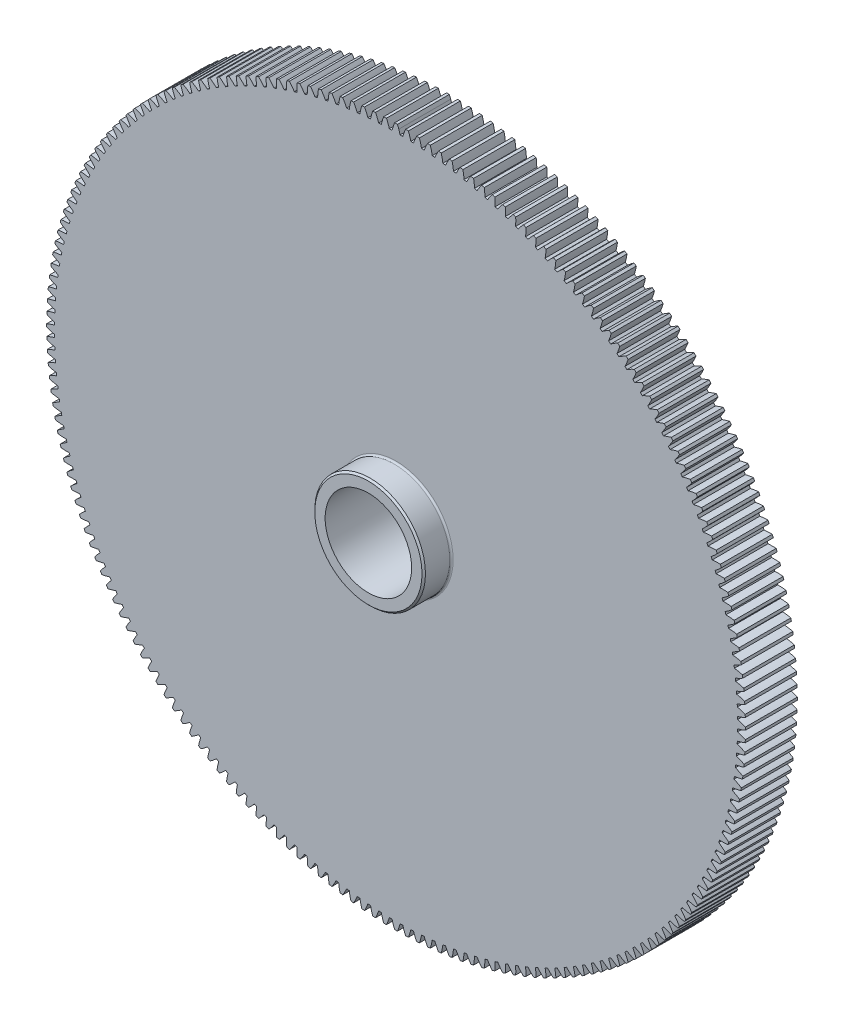
SolidWorks part; units mm, degrees
material "Сталь 45 ГОСТ 1050-88"
ref_plane "Front Plane" through (0, 0, 0) normal (0, 0, 1) x (1, 0, 0)
ref_plane "Top Plane" through (0, 0, 0) normal (0, 1, 0) x (1, 0, 0)
ref_plane "Right Plane" through (0, 0, 0) normal (1, 0, 0) x (0, 0, -1)
ref_plane "Ebene1" through (0, 0, 15) normal (0, 0, 1) x (1, 0, 0)
sketch "Skizze1" plane through (0, 0, 15) normal (0, 0, 1) x (1, 0, 0)
  arc A0 (-1.9388, 98.731) -> (-2.776, 100.9618) centre (-16.7744, 94.436) ccw
  arc A1 (-2.776, 100.9618) -> (-3.5689, 100.9369) centre (0, 0) ccw
  arc A2 (-3.5689, 100.9369) -> (-4.2644, 98.6579) centre (10.8116, 95.3029) ccw
  arc A3 (-4.2644, 98.6579) -> (-5.0391, 98.6213) centre (0, 0) ccw
  arc A4 (-5.0391, 98.6213) -> (-5.946, 100.8248) centre (-19.7324, 93.8625) ccw
  arc A5 (-5.946, 100.8248) -> (-6.7376, 100.775) centre (0, 0) ccw
  arc A6 (-6.7376, 100.775) -> (-7.3612, 98.4753) centre (7.8127, 95.5955) ccw
  arc A7 (-7.3612, 98.4753) -> (-8.1344, 98.4144) centre (0, 0) ccw
  arc A8 (-8.1344, 98.4144) -> (-9.11, 100.5883) centre (-22.671, 93.1964) ccw
  arc A9 (-9.11, 100.5883) -> (-9.8997, 100.5137) centre (0, 0) ccw
  arc A10 (-9.8997, 100.5137) -> (-10.4507, 98.1954) centre (4.8061, 95.7937) ccw
  arc A11 (-10.4507, 98.1954) -> (-11.2216, 98.1103) centre (0, 0) ccw
  arc A12 (-11.2216, 98.1103) -> (-12.2651, 100.2525) centre (-25.5872, 92.4383) ccw
  arc A13 (-12.2651, 100.2525) -> (-13.0521, 100.1531) centre (0, 0) ccw
  arc A14 (-13.0521, 100.1531) -> (-13.53, 97.8187) centre (1.7948, 95.8974) ccw
  arc A15 (-13.53, 97.8187) -> (-14.2978, 97.7094) centre (0, 0) ccw
  arc A16 (-14.2978, 97.7094) -> (-15.408, 99.8178) centre (-28.4781, 91.589) ccw
  arc A17 (-15.408, 99.8178) -> (-16.1915, 99.6937) centre (0, 0) ccw
  arc A18 (-16.1915, 99.6937) -> (-16.5959, 97.3455) centre (-1.2183, 95.9065) ccw
  arc A19 (-16.5959, 97.3455) -> (-17.3599, 97.2121) centre (0, 0) ccw
  arc A20 (-17.3599, 97.2121) -> (-18.5358, 99.2846) centre (-31.3409, 90.6492) ccw
  arc A21 (-18.5358, 99.2846) -> (-19.315, 99.1359) centre (0, 0) ccw
  arc A22 (-19.315, 99.1359) -> (-19.6454, 96.7761) centre (-4.2302, 95.8209) ccw
  arc A23 (-19.6454, 96.7761) -> (-20.4048, 96.6189) centre (0, 0) ccw
  arc A24 (-20.4048, 96.6189) -> (-21.6452, 98.6534) centre (-34.1728, 89.6201) ccw
  arc A25 (-21.6452, 98.6534) -> (-22.4194, 98.4803) centre (0, 0) ccw
  arc A26 (-22.4194, 98.4803) -> (-22.6755, 96.1113) centre (-7.2379, 95.6407) ccw
  arc A27 (-22.6755, 96.1113) -> (-23.4296, 95.9303) centre (0, 0) ccw
  arc A28 (-23.4296, 95.9303) -> (-24.7333, 97.9248) centre (-36.971, 88.5025) ccw
  arc A29 (-24.7333, 97.9248) -> (-25.5016, 97.7275) centre (0, 0) ccw
  arc A30 (-25.5016, 97.7275) -> (-25.6832, 95.3516) centre (-10.2385, 95.3662) ccw
  arc A31 (-25.6832, 95.3516) -> (-26.4313, 95.147) centre (0, 0) ccw
  arc A32 (-26.4313, 95.147) -> (-27.797, 97.0996) centre (-39.7327, 87.2975) ccw
  arc A33 (-27.797, 97.0996) -> (-28.5588, 96.8783) centre (0, 0) ccw
  arc A34 (-28.5588, 96.8783) -> (-28.6656, 94.4979) centre (-13.2289, 94.9975) ccw
  arc A35 (-28.6656, 94.4979) -> (-29.4069, 94.2698) centre (0, 0) ccw
  arc A36 (-29.4069, 94.2698) -> (-30.8333, 96.1785) centre (-42.4551, 86.0064) ccw
  arc A37 (-30.8333, 96.1785) -> (-31.5877, 95.9334) centre (0, 0) ccw
  arc A38 (-31.5877, 95.9334) -> (-31.6197, 93.5508) centre (-16.2064, 94.5351) ccw
  arc A39 (-31.6197, 93.5508) -> (-32.3535, 93.2996) centre (0, 0) ccw
  arc A40 (-32.3535, 93.2996) -> (-33.8391, 95.1626) centre (-45.1357, 84.6304) ccw
  arc A41 (-33.8391, 95.1626) -> (-34.5854, 94.8939) centre (0, 0) ccw
  arc A42 (-34.5854, 94.8939) -> (-34.5426, 92.5115) centre (-19.1678, 93.9794) ccw
  arc A43 (-34.5426, 92.5115) -> (-35.2681, 92.2373) centre (0, 0) ccw
  arc A44 (-35.2681, 92.2373) -> (-36.8115, 94.0527) centre (-47.7718, 83.1709) ccw
  arc A45 (-36.8115, 94.0527) -> (-37.5491, 93.7607) centre (0, 0) ccw
  arc A46 (-37.5491, 93.7607) -> (-37.4314, 91.3808) centre (-22.1103, 93.331) ccw
  arc A47 (-37.4314, 91.3808) -> (-38.148, 91.084) centre (0, 0) ccw
  arc A48 (-38.148, 91.084) -> (-39.7476, 92.85) centre (-50.3606, 81.6293) ccw
  arc A49 (-39.7476, 92.85) -> (-40.4756, 92.535) centre (0, 0) ccw
  arc A50 (-40.4756, 92.535) -> (-40.2833, 90.16) centre (-25.031, 92.5904) ccw
  arc A51 (-40.2833, 90.16) -> (-40.9902, 89.8408) centre (0, 0) ccw
  arc A52 (-40.9902, 89.8408) -> (-42.6445, 91.5557) centre (-52.8998, 80.0072) ccw
  arc A53 (-42.6445, 91.5557) -> (-43.3623, 91.218) centre (0, 0) ccw
  arc A54 (-43.3623, 91.218) -> (-43.0954, 88.8501) centre (-27.927, 91.7585) ccw
  arc A55 (-43.0954, 88.8501) -> (-43.7919, 88.5089) centre (0, 0) ccw
  arc A56 (-43.7919, 88.5089) -> (-45.4993, 90.171) centre (-55.3868, 78.3061) ccw
  arc A57 (-45.4993, 90.171) -> (-46.2061, 89.8109) centre (0, 0) ccw
  arc A58 (-46.2061, 89.8109) -> (-45.865, 87.4526) centre (-30.7954, 90.836) ccw
  arc A59 (-45.865, 87.4526) -> (-46.5504, 87.0897) centre (0, 0) ccw
  arc A60 (-46.5504, 87.0897) -> (-48.3092, 88.6974) centre (-57.8191, 76.5277) ccw
  arc A61 (-48.3092, 88.6974) -> (-49.0043, 88.3152) centre (0, 0) ccw
  arc A62 (-49.0043, 88.3152) -> (-48.5893, 85.9688) centre (-33.6334, 89.8239) ccw
  arc A63 (-48.5893, 85.9688) -> (-49.263, 85.5846) centre (0, 0) ccw
  arc A64 (-49.263, 85.5846) -> (-51.0714, 87.1362) centre (-60.1944, 74.6738) ccw
  arc A65 (-51.0714, 87.1362) -> (-51.7542, 86.7324) centre (0, 0) ccw
  arc A66 (-51.7542, 86.7324) -> (-51.2657, 84.4002) centre (-36.4383, 88.7231) ccw
  arc A67 (-51.2657, 84.4002) -> (-51.927, 83.9949) centre (0, 0) ccw
  arc A68 (-51.927, 83.9949) -> (-53.7832, 85.489) centre (-62.5103, 72.7462) ccw
  arc A69 (-53.7832, 85.489) -> (-54.453, 85.0639) centre (0, 0) ccw
  arc A70 (-54.453, 85.0639) -> (-53.8915, 82.7482) centre (-39.2071, 87.5348) ccw
  arc A71 (-53.8915, 82.7482) -> (-54.5397, 82.3224) centre (0, 0) ccw
  arc A72 (-54.5397, 82.3224) -> (-56.4419, 83.7574) centre (-64.7644, 70.7468) ccw
  arc A73 (-56.4419, 83.7574) -> (-57.098, 83.3116) centre (0, 0) ccw
  arc A74 (-57.098, 83.3116) -> (-56.4641, 81.0146) centre (-41.9373, 86.2601) ccw
  arc A75 (-56.4641, 81.0146) -> (-57.0986, 80.5687) centre (0, 0) ccw
  arc A76 (-57.0986, 80.5687) -> (-59.045, 81.9432) centre (-66.9547, 68.6776) ccw
  arc A77 (-59.045, 81.9432) -> (-59.6867, 81.477) centre (0, 0) ccw
  arc A78 (-59.6867, 81.477) -> (-58.9809, 79.2011) centre (-44.6261, 84.9002) ccw
  arc A79 (-58.9809, 79.2011) -> (-59.6011, 78.7354) centre (0, 0) ccw
  arc A80 (-59.6011, 78.7354) -> (-61.5897, 80.0481) centre (-69.0788, 66.5406) ccw
  arc A81 (-61.5897, 80.0481) -> (-62.2165, 79.5619) centre (0, 0) ccw
  arc A82 (-62.2165, 79.5619) -> (-61.4396, 77.3094) centre (-47.2709, 83.4566) ccw
  arc A83 (-61.4396, 77.3094) -> (-62.0449, 76.8244) centre (0, 0) ccw
  arc A84 (-62.0449, 76.8244) -> (-64.0737, 78.0741) centre (-71.1349, 64.3379) ccw
  arc A85 (-64.0737, 78.0741) -> (-64.6849, 77.5684) centre (0, 0) ccw
  arc A86 (-64.6849, 77.5684) -> (-63.8376, 75.3414) centre (-49.869, 81.9306) ccw
  arc A87 (-63.8376, 75.3414) -> (-64.4274, 74.8377) centre (0, 0) ccw
  arc A88 (-64.4274, 74.8377) -> (-66.4945, 76.0229) centre (-73.1207, 62.0718) ccw
  arc A89 (-66.4945, 76.0229) -> (-67.0895, 75.4983) centre (0, 0) ccw
  arc A90 (-67.0895, 75.4983) -> (-66.1727, 73.299) centre (-52.4179, 80.3237) ccw
  arc A91 (-66.1727, 73.299) -> (-66.7463, 72.777) centre (0, 0) ccw
  arc A92 (-66.7463, 72.777) -> (-68.8496, 73.8968) centre (-75.0343, 59.7444) ccw
  arc A93 (-68.8496, 73.8968) -> (-69.4279, 73.3538) centre (0, 0) ccw
  arc A94 (-69.4279, 73.3538) -> (-68.4424, 71.1843) centre (-54.915, 78.6376) ccw
  arc A95 (-68.4424, 71.1843) -> (-68.9993, 70.6446) centre (0, 0) ccw
  arc A96 (-68.9993, 70.6446) -> (-71.1368, 71.6977) centre (-76.8739, 57.358) ccw
  arc A97 (-71.1368, 71.6977) -> (-71.6977, 71.1368) centre (0, 0) ccw
  arc A98 (-71.6977, 71.1368) -> (-70.6446, 68.9993) centre (-57.358, 76.8739) ccw
  arc A99 (-70.6446, 68.9993) -> (-71.1843, 68.4424) centre (0, 0) ccw
  arc A100 (-71.1843, 68.4424) -> (-73.3538, 69.4279) centre (-78.6376, 54.915) ccw
  arc A101 (-73.3538, 69.4279) -> (-73.8968, 68.8496) centre (0, 0) ccw
  arc A102 (-73.8968, 68.8496) -> (-72.777, 66.7463) centre (-59.7444, 75.0343) ccw
  arc A103 (-72.777, 66.7463) -> (-73.299, 66.1727) centre (0, 0) ccw
  arc A104 (-73.299, 66.1727) -> (-75.4983, 67.0895) centre (-80.3237, 52.4179) ccw
  arc A105 (-75.4983, 67.0895) -> (-76.0229, 66.4945) centre (0, 0) ccw
  arc A106 (-76.0229, 66.4945) -> (-74.8377, 64.4274) centre (-62.0718, 73.1207) ccw
  arc A107 (-74.8377, 64.4274) -> (-75.3414, 63.8376) centre (0, 0) ccw
  arc A108 (-75.3414, 63.8376) -> (-77.5684, 64.6849) centre (-81.9306, 49.869) ccw
  arc A109 (-77.5684, 64.6849) -> (-78.0741, 64.0737) centre (0, 0) ccw
  arc A110 (-78.0741, 64.0737) -> (-76.8244, 62.0449) centre (-64.3379, 71.1349) ccw
  arc A111 (-76.8244, 62.0449) -> (-77.3094, 61.4396) centre (0, 0) ccw
  arc A112 (-77.3094, 61.4396) -> (-79.5619, 62.2165) centre (-83.4566, 47.2709) ccw
  arc A113 (-79.5619, 62.2165) -> (-80.0481, 61.5897) centre (0, 0) ccw
  arc A114 (-80.0481, 61.5897) -> (-78.7354, 59.6011) centre (-66.5406, 69.0788) ccw
  arc A115 (-78.7354, 59.6011) -> (-79.2011, 58.9809) centre (0, 0) ccw
  arc A116 (-79.2011, 58.9809) -> (-81.477, 59.6867) centre (-84.9002, 44.6261) ccw
  arc A117 (-81.477, 59.6867) -> (-81.9432, 59.045) centre (0, 0) ccw
  arc A118 (-81.9432, 59.045) -> (-80.5687, 57.0986) centre (-68.6776, 66.9547) ccw
  arc A119 (-80.5687, 57.0986) -> (-81.0146, 56.4641) centre (0, 0) ccw
  arc A120 (-81.0146, 56.4641) -> (-83.3116, 57.098) centre (-86.2601, 41.9373) ccw
  arc A121 (-83.3116, 57.098) -> (-83.7574, 56.4419) centre (0, 0) ccw
  arc A122 (-83.7574, 56.4419) -> (-82.3224, 54.5397) centre (-70.7468, 64.7644) ccw
  arc A123 (-82.3224, 54.5397) -> (-82.7482, 53.8915) centre (0, 0) ccw
  arc A124 (-82.7482, 53.8915) -> (-85.0639, 54.453) centre (-87.5348, 39.2071) ccw
  arc A125 (-85.0639, 54.453) -> (-85.489, 53.7832) centre (0, 0) ccw
  arc A126 (-85.489, 53.7832) -> (-83.9949, 51.927) centre (-72.7462, 62.5103) ccw
  arc A127 (-83.9949, 51.927) -> (-84.4002, 51.2657) centre (0, 0) ccw
  arc A128 (-84.4002, 51.2657) -> (-86.7324, 51.7542) centre (-88.7231, 36.4383) ccw
  arc A129 (-86.7324, 51.7542) -> (-87.1362, 51.0714) centre (0, 0) ccw
  arc A130 (-87.1362, 51.0714) -> (-85.5846, 49.263) centre (-74.6738, 60.1944) ccw
  arc A131 (-85.5846, 49.263) -> (-85.9688, 48.5893) centre (0, 0) ccw
  arc A132 (-85.9688, 48.5893) -> (-88.3152, 49.0043) centre (-89.8239, 33.6334) ccw
  arc A133 (-88.3152, 49.0043) -> (-88.6974, 48.3092) centre (0, 0) ccw
  arc A134 (-88.6974, 48.3092) -> (-87.0897, 46.5504) centre (-76.5277, 57.8191) ccw
  arc A135 (-87.0897, 46.5504) -> (-87.4526, 45.865) centre (0, 0) ccw
  arc A136 (-87.4526, 45.865) -> (-89.8109, 46.2061) centre (-90.836, 30.7954) ccw
  arc A137 (-89.8109, 46.2061) -> (-90.171, 45.4993) centre (0, 0) ccw
  arc A138 (-90.171, 45.4993) -> (-88.5089, 43.7919) centre (-78.3061, 55.3868) ccw
  arc A139 (-88.5089, 43.7919) -> (-88.8501, 43.0954) centre (0, 0) ccw
  arc A140 (-88.8501, 43.0954) -> (-91.218, 43.3623) centre (-91.7585, 27.927) ccw
  arc A141 (-91.218, 43.3623) -> (-91.5557, 42.6445) centre (0, 0) ccw
  arc A142 (-91.5557, 42.6445) -> (-89.8408, 40.9902) centre (-80.0072, 52.8998) ccw
  arc A143 (-89.8408, 40.9902) -> (-90.16, 40.2833) centre (0, 0) ccw
  arc A144 (-90.16, 40.2833) -> (-92.535, 40.4756) centre (-92.5904, 25.031) ccw
  arc A145 (-92.535, 40.4756) -> (-92.85, 39.7476) centre (0, 0) ccw
  arc A146 (-92.85, 39.7476) -> (-91.084, 38.148) centre (-81.6293, 50.3606) ccw
  arc A147 (-91.084, 38.148) -> (-91.3808, 37.4314) centre (0, 0) ccw
  arc A148 (-91.3808, 37.4314) -> (-93.7607, 37.5491) centre (-93.331, 22.1103) ccw
  arc A149 (-93.7607, 37.5491) -> (-94.0527, 36.8115) centre (0, 0) ccw
  arc A150 (-94.0527, 36.8115) -> (-92.2373, 35.2681) centre (-83.1709, 47.7718) ccw
  arc A151 (-92.2373, 35.2681) -> (-92.5115, 34.5426) centre (0, 0) ccw
  arc A152 (-92.5115, 34.5426) -> (-94.8939, 34.5854) centre (-93.9794, 19.1678) ccw
  arc A153 (-94.8939, 34.5854) -> (-95.1626, 33.8391) centre (0, 0) ccw
  arc A154 (-95.1626, 33.8391) -> (-93.2996, 32.3535) centre (-84.6304, 45.1357) ccw
  arc A155 (-93.2996, 32.3535) -> (-93.5508, 31.6197) centre (0, 0) ccw
  arc A156 (-93.5508, 31.6197) -> (-95.9334, 31.5877) centre (-94.5351, 16.2064) ccw
  arc A157 (-95.9334, 31.5877) -> (-96.1785, 30.8333) centre (0, 0) ccw
  arc A158 (-96.1785, 30.8333) -> (-94.2698, 29.4069) centre (-86.0064, 42.4551) ccw
  arc A159 (-94.2698, 29.4069) -> (-94.4979, 28.6656) centre (0, 0) ccw
  arc A160 (-94.4979, 28.6656) -> (-96.8783, 28.5588) centre (-94.9975, 13.2289) ccw
  arc A161 (-96.8783, 28.5588) -> (-97.0996, 27.797) centre (0, 0) ccw
  arc A162 (-97.0996, 27.797) -> (-95.147, 26.4313) centre (-87.2975, 39.7327) ccw
  arc A163 (-95.147, 26.4313) -> (-95.3516, 25.6832) centre (0, 0) ccw
  arc A164 (-95.3516, 25.6832) -> (-97.7275, 25.5016) centre (-95.3662, 10.2385) ccw
  arc A165 (-97.7275, 25.5016) -> (-97.9248, 24.7333) centre (0, 0) ccw
  arc A166 (-97.9248, 24.7333) -> (-95.9303, 23.4296) centre (-88.5025, 36.971) ccw
  arc A167 (-95.9303, 23.4296) -> (-96.1113, 22.6755) centre (0, 0) ccw
  arc A168 (-96.1113, 22.6755) -> (-98.4803, 22.4194) centre (-95.6407, 7.2379) ccw
  arc A169 (-98.4803, 22.4194) -> (-98.6534, 21.6452) centre (0, 0) ccw
  arc A170 (-98.6534, 21.6452) -> (-96.6189, 20.4048) centre (-89.6201, 34.1728) ccw
  arc A171 (-96.6189, 20.4048) -> (-96.7761, 19.6454) centre (0, 0) ccw
  arc A172 (-96.7761, 19.6454) -> (-99.1359, 19.315) centre (-95.8209, 4.2302) ccw
  arc A173 (-99.1359, 19.315) -> (-99.2846, 18.5358) centre (0, 0) ccw
  arc A174 (-99.2846, 18.5358) -> (-97.2121, 17.3599) centre (-90.6492, 31.3409) ccw
  arc A175 (-97.2121, 17.3599) -> (-97.3455, 16.5959) centre (0, 0) ccw
  arc A176 (-97.3455, 16.5959) -> (-99.6937, 16.1915) centre (-95.9065, 1.2183) ccw
  arc A177 (-99.6937, 16.1915) -> (-99.8178, 15.408) centre (0, 0) ccw
  arc A178 (-99.8178, 15.408) -> (-97.7094, 14.2978) centre (-91.589, 28.4781) ccw
  arc A179 (-97.7094, 14.2978) -> (-97.8187, 13.53) centre (0, 0) ccw
  arc A180 (-97.8187, 13.53) -> (-100.1531, 13.0521) centre (-95.8974, -1.7948) ccw
  arc A181 (-100.1531, 13.0521) -> (-100.2525, 12.2651) centre (0, 0) ccw
  arc A182 (-100.2525, 12.2651) -> (-98.1103, 11.2216) centre (-92.4383, 25.5872) ccw
  arc A183 (-98.1103, 11.2216) -> (-98.1954, 10.4507) centre (0, 0) ccw
  arc A184 (-98.1954, 10.4507) -> (-100.5137, 9.8997) centre (-95.7937, -4.8061) ccw
  arc A185 (-100.5137, 9.8997) -> (-100.5883, 9.11) centre (0, 0) ccw
  arc A186 (-100.5883, 9.11) -> (-98.4144, 8.1344) centre (-93.1964, 22.671) ccw
  arc A187 (-98.4144, 8.1344) -> (-98.4753, 7.3612) centre (0, 0) ccw
  arc A188 (-98.4753, 7.3612) -> (-100.775, 6.7376) centre (-95.5955, -7.8127) ccw
  arc A189 (-100.775, 6.7376) -> (-100.8248, 5.946) centre (0, 0) ccw
  arc A190 (-100.8248, 5.946) -> (-98.6213, 5.0391) centre (-93.8625, 19.7324) ccw
  arc A191 (-98.6213, 5.0391) -> (-98.6579, 4.2644) centre (0, 0) ccw
  arc A192 (-98.6579, 4.2644) -> (-100.9369, 3.5689) centre (-95.3029, -10.8116) ccw
  arc A193 (-100.9369, 3.5689) -> (-100.9618, 2.776) centre (0, 0) ccw
  arc A194 (-100.9618, 2.776) -> (-98.731, 1.9388) centre (-94.436, 16.7744) ccw
  arc A195 (-98.731, 1.9388) -> (-98.7431, 1.1633) centre (0, 0) ccw
  arc A196 (-98.7431, 1.1633) -> (-100.9992, 0.3966) centre (-94.9163, -13.7998) ccw
  arc A197 (-100.9992, 0.3966) -> (-100.9992, -0.3966) centre (0, 0) ccw
  arc A198 (-100.9992, -0.3966) -> (-98.7431, -1.1633) centre (-94.9163, 13.7998) ccw
  arc A199 (-98.7431, -1.1633) -> (-98.731, -1.9388) centre (0, 0) ccw
  arc A200 (-98.731, -1.9388) -> (-100.9618, -2.776) centre (-94.436, -16.7744) ccw
  arc A201 (-100.9618, -2.776) -> (-100.9369, -3.5689) centre (0, 0) ccw
  arc A202 (-100.9369, -3.5689) -> (-98.6579, -4.2644) centre (-95.3029, 10.8116) ccw
  arc A203 (-98.6579, -4.2644) -> (-98.6213, -5.0391) centre (0, 0) ccw
  arc A204 (-98.6213, -5.0391) -> (-100.8248, -5.946) centre (-93.8625, -19.7324) ccw
  arc A205 (-100.8248, -5.946) -> (-100.775, -6.7376) centre (0, 0) ccw
  arc A206 (-100.775, -6.7376) -> (-98.4753, -7.3612) centre (-95.5955, 7.8127) ccw
  arc A207 (-98.4753, -7.3612) -> (-98.4144, -8.1344) centre (0, 0) ccw
  arc A208 (-98.4144, -8.1344) -> (-100.5883, -9.11) centre (-93.1964, -22.671) ccw
  arc A209 (-100.5883, -9.11) -> (-100.5137, -9.8997) centre (0, 0) ccw
  arc A210 (-100.5137, -9.8997) -> (-98.1954, -10.4507) centre (-95.7937, 4.8061) ccw
  arc A211 (-98.1954, -10.4507) -> (-98.1103, -11.2216) centre (0, 0) ccw
  arc A212 (-98.1103, -11.2216) -> (-100.2525, -12.2651) centre (-92.4383, -25.5872) ccw
  arc A213 (-100.2525, -12.2651) -> (-100.1531, -13.0521) centre (0, 0) ccw
  arc A214 (-100.1531, -13.0521) -> (-97.8187, -13.53) centre (-95.8974, 1.7948) ccw
  arc A215 (-97.8187, -13.53) -> (-97.7094, -14.2978) centre (0, 0) ccw
  arc A216 (-97.7094, -14.2978) -> (-99.8178, -15.408) centre (-91.589, -28.4781) ccw
  arc A217 (-99.8178, -15.408) -> (-99.6937, -16.1915) centre (0, 0) ccw
  arc A218 (-99.6937, -16.1915) -> (-97.3455, -16.5959) centre (-95.9065, -1.2183) ccw
  arc A219 (-97.3455, -16.5959) -> (-97.2121, -17.3599) centre (0, 0) ccw
  arc A220 (-97.2121, -17.3599) -> (-99.2846, -18.5358) centre (-90.6492, -31.3409) ccw
  arc A221 (-99.2846, -18.5358) -> (-99.1359, -19.315) centre (0, 0) ccw
  arc A222 (-99.1359, -19.315) -> (-96.7761, -19.6454) centre (-95.8209, -4.2302) ccw
  arc A223 (-96.7761, -19.6454) -> (-96.6189, -20.4048) centre (0, 0) ccw
  arc A224 (-96.6189, -20.4048) -> (-98.6534, -21.6452) centre (-89.6201, -34.1728) ccw
  arc A225 (-98.6534, -21.6452) -> (-98.4803, -22.4194) centre (0, 0) ccw
  arc A226 (-98.4803, -22.4194) -> (-96.1113, -22.6755) centre (-95.6407, -7.2379) ccw
  arc A227 (-96.1113, -22.6755) -> (-95.9303, -23.4296) centre (0, 0) ccw
  arc A228 (-95.9303, -23.4296) -> (-97.9248, -24.7333) centre (-88.5025, -36.971) ccw
  arc A229 (-97.9248, -24.7333) -> (-97.7275, -25.5016) centre (0, 0) ccw
  arc A230 (-97.7275, -25.5016) -> (-95.3516, -25.6832) centre (-95.3662, -10.2385) ccw
  arc A231 (-95.3516, -25.6832) -> (-95.147, -26.4313) centre (0, 0) ccw
  arc A232 (-95.147, -26.4313) -> (-97.0996, -27.797) centre (-87.2975, -39.7327) ccw
  arc A233 (-97.0996, -27.797) -> (-96.8783, -28.5588) centre (0, 0) ccw
  arc A234 (-96.8783, -28.5588) -> (-94.4979, -28.6656) centre (-94.9975, -13.2289) ccw
  arc A235 (-94.4979, -28.6656) -> (-94.2698, -29.4069) centre (0, 0) ccw
  arc A236 (-94.2698, -29.4069) -> (-96.1785, -30.8333) centre (-86.0064, -42.4551) ccw
  arc A237 (-96.1785, -30.8333) -> (-95.9334, -31.5877) centre (0, 0) ccw
  arc A238 (-95.9334, -31.5877) -> (-93.5508, -31.6197) centre (-94.5351, -16.2064) ccw
  arc A239 (-93.5508, -31.6197) -> (-93.2996, -32.3535) centre (0, 0) ccw
  arc A240 (-93.2996, -32.3535) -> (-95.1626, -33.8391) centre (-84.6304, -45.1357) ccw
  arc A241 (-95.1626, -33.8391) -> (-94.8939, -34.5854) centre (0, 0) ccw
  arc A242 (-94.8939, -34.5854) -> (-92.5115, -34.5426) centre (-93.9794, -19.1678) ccw
  arc A243 (-92.5115, -34.5426) -> (-92.2373, -35.2681) centre (0, 0) ccw
  arc A244 (-92.2373, -35.2681) -> (-94.0527, -36.8115) centre (-83.1709, -47.7718) ccw
  arc A245 (-94.0527, -36.8115) -> (-93.7607, -37.5491) centre (0, 0) ccw
  arc A246 (-93.7607, -37.5491) -> (-91.3808, -37.4314) centre (-93.331, -22.1103) ccw
  arc A247 (-91.3808, -37.4314) -> (-91.084, -38.148) centre (0, 0) ccw
  arc A248 (-91.084, -38.148) -> (-92.85, -39.7476) centre (-81.6293, -50.3606) ccw
  arc A249 (-92.85, -39.7476) -> (-92.535, -40.4756) centre (0, 0) ccw
  arc A250 (-92.535, -40.4756) -> (-90.16, -40.2833) centre (-92.5904, -25.031) ccw
  arc A251 (-90.16, -40.2833) -> (-89.8408, -40.9902) centre (0, 0) ccw
  arc A252 (-89.8408, -40.9902) -> (-91.5557, -42.6445) centre (-80.0072, -52.8998) ccw
  arc A253 (-91.5557, -42.6445) -> (-91.218, -43.3623) centre (0, 0) ccw
  arc A254 (-91.218, -43.3623) -> (-88.8501, -43.0954) centre (-91.7585, -27.927) ccw
  arc A255 (-88.8501, -43.0954) -> (-88.5089, -43.7919) centre (0, 0) ccw
  arc A256 (-88.5089, -43.7919) -> (-90.171, -45.4993) centre (-78.3061, -55.3868) ccw
  arc A257 (-90.171, -45.4993) -> (-89.8109, -46.2061) centre (0, 0) ccw
  arc A258 (-89.8109, -46.2061) -> (-87.4526, -45.865) centre (-90.836, -30.7954) ccw
  arc A259 (-87.4526, -45.865) -> (-87.0897, -46.5504) centre (0, 0) ccw
  arc A260 (-87.0897, -46.5504) -> (-88.6974, -48.3092) centre (-76.5277, -57.8191) ccw
  arc A261 (-88.6974, -48.3092) -> (-88.3152, -49.0043) centre (0, 0) ccw
  arc A262 (-88.3152, -49.0043) -> (-85.9688, -48.5893) centre (-89.8239, -33.6334) ccw
  arc A263 (-85.9688, -48.5893) -> (-85.5846, -49.263) centre (0, 0) ccw
  arc A264 (-85.5846, -49.263) -> (-87.1362, -51.0714) centre (-74.6738, -60.1944) ccw
  arc A265 (-87.1362, -51.0714) -> (-86.7324, -51.7542) centre (0, 0) ccw
  arc A266 (-86.7324, -51.7542) -> (-84.4002, -51.2657) centre (-88.7231, -36.4383) ccw
  arc A267 (-84.4002, -51.2657) -> (-83.9949, -51.927) centre (0, 0) ccw
  arc A268 (-83.9949, -51.927) -> (-85.489, -53.7832) centre (-72.7462, -62.5103) ccw
  arc A269 (-85.489, -53.7832) -> (-85.0639, -54.453) centre (0, 0) ccw
  arc A270 (-85.0639, -54.453) -> (-82.7482, -53.8915) centre (-87.5348, -39.2071) ccw
  arc A271 (-82.7482, -53.8915) -> (-82.3224, -54.5397) centre (0, 0) ccw
  arc A272 (-82.3224, -54.5397) -> (-83.7574, -56.4419) centre (-70.7468, -64.7644) ccw
  arc A273 (-83.7574, -56.4419) -> (-83.3116, -57.098) centre (0, 0) ccw
  arc A274 (-83.3116, -57.098) -> (-81.0146, -56.4641) centre (-86.2601, -41.9373) ccw
  arc A275 (-81.0146, -56.4641) -> (-80.5687, -57.0986) centre (0, 0) ccw
  arc A276 (-80.5687, -57.0986) -> (-81.9432, -59.045) centre (-68.6776, -66.9547) ccw
  arc A277 (-81.9432, -59.045) -> (-81.477, -59.6867) centre (0, 0) ccw
  arc A278 (-81.477, -59.6867) -> (-79.2011, -58.9809) centre (-84.9002, -44.6261) ccw
  arc A279 (-79.2011, -58.9809) -> (-78.7354, -59.6011) centre (0, 0) ccw
  arc A280 (-78.7354, -59.6011) -> (-80.0481, -61.5897) centre (-66.5406, -69.0788) ccw
  arc A281 (-80.0481, -61.5897) -> (-79.5619, -62.2165) centre (0, 0) ccw
  arc A282 (-79.5619, -62.2165) -> (-77.3094, -61.4396) centre (-83.4566, -47.2709) ccw
  arc A283 (-77.3094, -61.4396) -> (-76.8244, -62.0449) centre (0, 0) ccw
  arc A284 (-76.8244, -62.0449) -> (-78.0741, -64.0737) centre (-64.3379, -71.1349) ccw
  arc A285 (-78.0741, -64.0737) -> (-77.5684, -64.6849) centre (0, 0) ccw
  arc A286 (-77.5684, -64.6849) -> (-75.3414, -63.8376) centre (-81.9306, -49.869) ccw
  arc A287 (-75.3414, -63.8376) -> (-74.8377, -64.4274) centre (0, 0) ccw
  arc A288 (-74.8377, -64.4274) -> (-76.0229, -66.4945) centre (-62.0718, -73.1207) ccw
  arc A289 (-76.0229, -66.4945) -> (-75.4983, -67.0895) centre (0, 0) ccw
  arc A290 (-75.4983, -67.0895) -> (-73.299, -66.1727) centre (-80.3237, -52.4179) ccw
  arc A291 (-73.299, -66.1727) -> (-72.777, -66.7463) centre (0, 0) ccw
  arc A292 (-72.777, -66.7463) -> (-73.8968, -68.8496) centre (-59.7444, -75.0343) ccw
  arc A293 (-73.8968, -68.8496) -> (-73.3538, -69.4279) centre (0, 0) ccw
  arc A294 (-73.3538, -69.4279) -> (-71.1843, -68.4424) centre (-78.6376, -54.915) ccw
  arc A295 (-71.1843, -68.4424) -> (-70.6446, -68.9993) centre (0, 0) ccw
  arc A296 (-70.6446, -68.9993) -> (-71.6977, -71.1368) centre (-57.358, -76.8739) ccw
  arc A297 (-71.6977, -71.1368) -> (-71.1368, -71.6977) centre (0, 0) ccw
  arc A298 (-71.1368, -71.6977) -> (-68.9993, -70.6446) centre (-76.8739, -57.358) ccw
  arc A299 (-68.9993, -70.6446) -> (-68.4424, -71.1843) centre (0, 0) ccw
  arc A300 (-68.4424, -71.1843) -> (-69.4279, -73.3538) centre (-54.915, -78.6376) ccw
  arc A301 (-69.4279, -73.3538) -> (-68.8496, -73.8968) centre (0, 0) ccw
  arc A302 (-68.8496, -73.8968) -> (-66.7463, -72.777) centre (-75.0343, -59.7444) ccw
  arc A303 (-66.7463, -72.777) -> (-66.1727, -73.299) centre (0, 0) ccw
  arc A304 (-66.1727, -73.299) -> (-67.0895, -75.4983) centre (-52.4179, -80.3237) ccw
  arc A305 (-67.0895, -75.4983) -> (-66.4945, -76.0229) centre (0, 0) ccw
  arc A306 (-66.4945, -76.0229) -> (-64.4274, -74.8377) centre (-73.1207, -62.0718) ccw
  arc A307 (-64.4274, -74.8377) -> (-63.8376, -75.3414) centre (0, 0) ccw
  arc A308 (-63.8376, -75.3414) -> (-64.6849, -77.5684) centre (-49.869, -81.9306) ccw
  arc A309 (-64.6849, -77.5684) -> (-64.0737, -78.0741) centre (0, 0) ccw
  arc A310 (-64.0737, -78.0741) -> (-62.0449, -76.8244) centre (-71.1349, -64.3379) ccw
  arc A311 (-62.0449, -76.8244) -> (-61.4396, -77.3094) centre (0, 0) ccw
  arc A312 (-61.4396, -77.3094) -> (-62.2165, -79.5619) centre (-47.2709, -83.4566) ccw
  arc A313 (-62.2165, -79.5619) -> (-61.5897, -80.0481) centre (0, 0) ccw
  arc A314 (-61.5897, -80.0481) -> (-59.6011, -78.7354) centre (-69.0788, -66.5406) ccw
  arc A315 (-59.6011, -78.7354) -> (-58.9809, -79.2011) centre (0, 0) ccw
  arc A316 (-58.9809, -79.2011) -> (-59.6867, -81.477) centre (-44.6261, -84.9002) ccw
  arc A317 (-59.6867, -81.477) -> (-59.045, -81.9432) centre (0, 0) ccw
  arc A318 (-59.045, -81.9432) -> (-57.0986, -80.5687) centre (-66.9547, -68.6776) ccw
  arc A319 (-57.0986, -80.5687) -> (-56.4641, -81.0146) centre (0, 0) ccw
  arc A320 (-56.4641, -81.0146) -> (-57.098, -83.3116) centre (-41.9373, -86.2601) ccw
  arc A321 (-57.098, -83.3116) -> (-56.4419, -83.7574) centre (0, 0) ccw
  arc A322 (-56.4419, -83.7574) -> (-54.5397, -82.3224) centre (-64.7644, -70.7468) ccw
  arc A323 (-54.5397, -82.3224) -> (-53.8915, -82.7482) centre (0, 0) ccw
  arc A324 (-53.8915, -82.7482) -> (-54.453, -85.0639) centre (-39.2071, -87.5348) ccw
  arc A325 (-54.453, -85.0639) -> (-53.7832, -85.489) centre (0, 0) ccw
  arc A326 (-53.7832, -85.489) -> (-51.927, -83.9949) centre (-62.5103, -72.7462) ccw
  arc A327 (-51.927, -83.9949) -> (-51.2657, -84.4002) centre (0, 0) ccw
  arc A328 (-51.2657, -84.4002) -> (-51.7542, -86.7324) centre (-36.4383, -88.7231) ccw
  arc A329 (-51.7542, -86.7324) -> (-51.0714, -87.1362) centre (0, 0) ccw
  arc A330 (-51.0714, -87.1362) -> (-49.263, -85.5846) centre (-60.1944, -74.6738) ccw
  arc A331 (-49.263, -85.5846) -> (-48.5893, -85.9688) centre (0, 0) ccw
  arc A332 (-48.5893, -85.9688) -> (-49.0043, -88.3152) centre (-33.6334, -89.8239) ccw
  arc A333 (-49.0043, -88.3152) -> (-48.3092, -88.6974) centre (0, 0) ccw
  arc A334 (-48.3092, -88.6974) -> (-46.5504, -87.0897) centre (-57.8191, -76.5277) ccw
  arc A335 (-46.5504, -87.0897) -> (-45.865, -87.4526) centre (0, 0) ccw
  arc A336 (-45.865, -87.4526) -> (-46.2061, -89.8109) centre (-30.7954, -90.836) ccw
  arc A337 (-46.2061, -89.8109) -> (-45.4993, -90.171) centre (0, 0) ccw
  arc A338 (-45.4993, -90.171) -> (-43.7919, -88.5089) centre (-55.3868, -78.3061) ccw
  arc A339 (-43.7919, -88.5089) -> (-43.0954, -88.8501) centre (0, 0) ccw
  arc A340 (-43.0954, -88.8501) -> (-43.3623, -91.218) centre (-27.927, -91.7585) ccw
  arc A341 (-43.3623, -91.218) -> (-42.6445, -91.5557) centre (0, 0) ccw
  arc A342 (-42.6445, -91.5557) -> (-40.9902, -89.8408) centre (-52.8998, -80.0072) ccw
  arc A343 (-40.9902, -89.8408) -> (-40.2833, -90.16) centre (0, 0) ccw
  arc A344 (-40.2833, -90.16) -> (-40.4756, -92.535) centre (-25.031, -92.5904) ccw
  arc A345 (-40.4756, -92.535) -> (-39.7476, -92.85) centre (0, 0) ccw
  arc A346 (-39.7476, -92.85) -> (-38.148, -91.084) centre (-50.3606, -81.6293) ccw
  arc A347 (-38.148, -91.084) -> (-37.4314, -91.3808) centre (0, 0) ccw
  arc A348 (-37.4314, -91.3808) -> (-37.5491, -93.7607) centre (-22.1103, -93.331) ccw
  arc A349 (-37.5491, -93.7607) -> (-36.8115, -94.0527) centre (0, 0) ccw
  arc A350 (-36.8115, -94.0527) -> (-35.2681, -92.2373) centre (-47.7718, -83.1709) ccw
  arc A351 (-35.2681, -92.2373) -> (-34.5426, -92.5115) centre (0, 0) ccw
  arc A352 (-34.5426, -92.5115) -> (-34.5854, -94.8939) centre (-19.1678, -93.9794) ccw
  arc A353 (-34.5854, -94.8939) -> (-33.8391, -95.1626) centre (0, 0) ccw
  arc A354 (-33.8391, -95.1626) -> (-32.3535, -93.2996) centre (-45.1357, -84.6304) ccw
  arc A355 (-32.3535, -93.2996) -> (-31.6197, -93.5508) centre (0, 0) ccw
  arc A356 (-31.6197, -93.5508) -> (-31.5877, -95.9334) centre (-16.2064, -94.5351) ccw
  arc A357 (-31.5877, -95.9334) -> (-30.8333, -96.1785) centre (0, 0) ccw
  arc A358 (-30.8333, -96.1785) -> (-29.4069, -94.2698) centre (-42.4551, -86.0064) ccw
  arc A359 (-29.4069, -94.2698) -> (-28.6656, -94.4979) centre (0, 0) ccw
  arc A360 (-28.6656, -94.4979) -> (-28.5588, -96.8783) centre (-13.2289, -94.9975) ccw
  arc A361 (-28.5588, -96.8783) -> (-27.797, -97.0996) centre (0, 0) ccw
  arc A362 (-27.797, -97.0996) -> (-26.4313, -95.147) centre (-39.7327, -87.2975) ccw
  arc A363 (-26.4313, -95.147) -> (-25.6832, -95.3516) centre (0, 0) ccw
  arc A364 (-25.6832, -95.3516) -> (-25.5016, -97.7275) centre (-10.2385, -95.3662) ccw
  arc A365 (-25.5016, -97.7275) -> (-24.7333, -97.9248) centre (0, 0) ccw
  arc A366 (-24.7333, -97.9248) -> (-23.4296, -95.9303) centre (-36.971, -88.5025) ccw
  arc A367 (-23.4296, -95.9303) -> (-22.6755, -96.1113) centre (0, 0) ccw
  arc A368 (-22.6755, -96.1113) -> (-22.4194, -98.4803) centre (-7.2379, -95.6407) ccw
  arc A369 (-22.4194, -98.4803) -> (-21.6452, -98.6534) centre (0, 0) ccw
  arc A370 (-21.6452, -98.6534) -> (-20.4048, -96.6189) centre (-34.1728, -89.6201) ccw
  arc A371 (-20.4048, -96.6189) -> (-19.6454, -96.7761) centre (0, 0) ccw
  arc A372 (-19.6454, -96.7761) -> (-19.315, -99.1359) centre (-4.2302, -95.8209) ccw
  arc A373 (-19.315, -99.1359) -> (-18.5358, -99.2846) centre (0, 0) ccw
  arc A374 (-18.5358, -99.2846) -> (-17.3599, -97.2121) centre (-31.3409, -90.6492) ccw
  arc A375 (-17.3599, -97.2121) -> (-16.5959, -97.3455) centre (0, 0) ccw
  arc A376 (-16.5959, -97.3455) -> (-16.1915, -99.6937) centre (-1.2183, -95.9065) ccw
  arc A377 (-16.1915, -99.6937) -> (-15.408, -99.8178) centre (0, 0) ccw
  arc A378 (-15.408, -99.8178) -> (-14.2978, -97.7094) centre (-28.4781, -91.589) ccw
  arc A379 (-14.2978, -97.7094) -> (-13.53, -97.8187) centre (0, 0) ccw
  arc A380 (-13.53, -97.8187) -> (-13.0521, -100.1531) centre (1.7948, -95.8974) ccw
  arc A381 (-13.0521, -100.1531) -> (-12.2651, -100.2525) centre (0, 0) ccw
  arc A382 (-12.2651, -100.2525) -> (-11.2216, -98.1103) centre (-25.5872, -92.4383) ccw
  arc A383 (-11.2216, -98.1103) -> (-10.4507, -98.1954) centre (0, 0) ccw
  arc A384 (-10.4507, -98.1954) -> (-9.8997, -100.5137) centre (4.8061, -95.7937) ccw
  arc A385 (-9.8997, -100.5137) -> (-9.11, -100.5883) centre (0, 0) ccw
  arc A386 (-9.11, -100.5883) -> (-8.1344, -98.4144) centre (-22.671, -93.1964) ccw
  arc A387 (-8.1344, -98.4144) -> (-7.3612, -98.4753) centre (0, 0) ccw
  arc A388 (-7.3612, -98.4753) -> (-6.7376, -100.775) centre (7.8127, -95.5955) ccw
  arc A389 (-6.7376, -100.775) -> (-5.946, -100.8248) centre (0, 0) ccw
  arc A390 (-5.946, -100.8248) -> (-5.0391, -98.6213) centre (-19.7324, -93.8625) ccw
  arc A391 (-5.0391, -98.6213) -> (-4.2644, -98.6579) centre (0, 0) ccw
  arc A392 (-4.2644, -98.6579) -> (-3.5689, -100.9369) centre (10.8116, -95.3029) ccw
  arc A393 (-3.5689, -100.9369) -> (-2.776, -100.9618) centre (0, 0) ccw
  arc A394 (-2.776, -100.9618) -> (-1.9388, -98.731) centre (-16.7744, -94.436) ccw
  arc A395 (-1.9388, -98.731) -> (-1.1633, -98.7431) centre (0, 0) ccw
  arc A396 (-1.1633, -98.7431) -> (-0.3966, -100.9992) centre (13.7998, -94.9163) ccw
  arc A397 (-0.3966, -100.9992) -> (0.3966, -100.9992) centre (0, 0) ccw
  arc A398 (0.3966, -100.9992) -> (1.1633, -98.7431) centre (-13.7998, -94.9163) ccw
  arc A399 (1.1633, -98.7431) -> (1.9388, -98.731) centre (0, 0) ccw
  arc A400 (1.9388, -98.731) -> (2.776, -100.9618) centre (16.7744, -94.436) ccw
  arc A401 (2.776, -100.9618) -> (3.5689, -100.9369) centre (0, 0) ccw
  arc A402 (3.5689, -100.9369) -> (4.2644, -98.6579) centre (-10.8116, -95.3029) ccw
  arc A403 (4.2644, -98.6579) -> (5.0391, -98.6213) centre (0, 0) ccw
  arc A404 (5.0391, -98.6213) -> (5.946, -100.8248) centre (19.7324, -93.8625) ccw
  arc A405 (5.946, -100.8248) -> (6.7376, -100.775) centre (0, 0) ccw
  arc A406 (6.7376, -100.775) -> (7.3612, -98.4753) centre (-7.8127, -95.5955) ccw
  arc A407 (7.3612, -98.4753) -> (8.1344, -98.4144) centre (0, 0) ccw
  arc A408 (8.1344, -98.4144) -> (9.11, -100.5883) centre (22.671, -93.1964) ccw
  arc A409 (9.11, -100.5883) -> (9.8997, -100.5137) centre (0, 0) ccw
  arc A410 (9.8997, -100.5137) -> (10.4507, -98.1954) centre (-4.8061, -95.7937) ccw
  arc A411 (10.4507, -98.1954) -> (11.2216, -98.1103) centre (0, 0) ccw
  arc A412 (11.2216, -98.1103) -> (12.2651, -100.2525) centre (25.5872, -92.4383) ccw
  arc A413 (12.2651, -100.2525) -> (13.0521, -100.1531) centre (0, 0) ccw
  arc A414 (13.0521, -100.1531) -> (13.53, -97.8187) centre (-1.7948, -95.8974) ccw
  arc A415 (13.53, -97.8187) -> (14.2978, -97.7094) centre (0, 0) ccw
  arc A416 (14.2978, -97.7094) -> (15.408, -99.8178) centre (28.4781, -91.589) ccw
  arc A417 (15.408, -99.8178) -> (16.1915, -99.6937) centre (0, 0) ccw
  arc A418 (16.1915, -99.6937) -> (16.5959, -97.3455) centre (1.2183, -95.9065) ccw
  arc A419 (16.5959, -97.3455) -> (17.3599, -97.2121) centre (0, 0) ccw
  arc A420 (17.3599, -97.2121) -> (18.5358, -99.2846) centre (31.3409, -90.6492) ccw
  arc A421 (18.5358, -99.2846) -> (19.315, -99.1359) centre (0, 0) ccw
  arc A422 (19.315, -99.1359) -> (19.6454, -96.7761) centre (4.2302, -95.8209) ccw
  arc A423 (19.6454, -96.7761) -> (20.4048, -96.6189) centre (0, 0) ccw
  arc A424 (20.4048, -96.6189) -> (21.6452, -98.6534) centre (34.1728, -89.6201) ccw
  arc A425 (21.6452, -98.6534) -> (22.4194, -98.4803) centre (0, 0) ccw
  arc A426 (22.4194, -98.4803) -> (22.6755, -96.1113) centre (7.2379, -95.6407) ccw
  arc A427 (22.6755, -96.1113) -> (23.4296, -95.9303) centre (0, 0) ccw
  arc A428 (23.4296, -95.9303) -> (24.7333, -97.9248) centre (36.971, -88.5025) ccw
  arc A429 (24.7333, -97.9248) -> (25.5016, -97.7275) centre (0, 0) ccw
  arc A430 (25.5016, -97.7275) -> (25.6832, -95.3516) centre (10.2385, -95.3662) ccw
  arc A431 (25.6832, -95.3516) -> (26.4313, -95.147) centre (0, 0) ccw
  arc A432 (26.4313, -95.147) -> (27.797, -97.0996) centre (39.7327, -87.2975) ccw
  arc A433 (27.797, -97.0996) -> (28.5588, -96.8783) centre (0, 0) ccw
  arc A434 (28.5588, -96.8783) -> (28.6656, -94.4979) centre (13.2289, -94.9975) ccw
  arc A435 (28.6656, -94.4979) -> (29.4069, -94.2698) centre (0, 0) ccw
  arc A436 (29.4069, -94.2698) -> (30.8333, -96.1785) centre (42.4551, -86.0064) ccw
  arc A437 (30.8333, -96.1785) -> (31.5877, -95.9334) centre (0, 0) ccw
  arc A438 (31.5877, -95.9334) -> (31.6197, -93.5508) centre (16.2064, -94.5351) ccw
  arc A439 (31.6197, -93.5508) -> (32.3535, -93.2996) centre (0, 0) ccw
  arc A440 (32.3535, -93.2996) -> (33.8391, -95.1626) centre (45.1357, -84.6304) ccw
  arc A441 (33.8391, -95.1626) -> (34.5854, -94.8939) centre (0, 0) ccw
  arc A442 (34.5854, -94.8939) -> (34.5426, -92.5115) centre (19.1678, -93.9794) ccw
  arc A443 (34.5426, -92.5115) -> (35.2681, -92.2373) centre (0, 0) ccw
  arc A444 (35.2681, -92.2373) -> (36.8115, -94.0527) centre (47.7718, -83.1709) ccw
  arc A445 (36.8115, -94.0527) -> (37.5491, -93.7607) centre (0, 0) ccw
  arc A446 (37.5491, -93.7607) -> (37.4314, -91.3808) centre (22.1103, -93.331) ccw
  arc A447 (37.4314, -91.3808) -> (38.148, -91.084) centre (0, 0) ccw
  arc A448 (38.148, -91.084) -> (39.7476, -92.85) centre (50.3606, -81.6293) ccw
  arc A449 (39.7476, -92.85) -> (40.4756, -92.535) centre (0, 0) ccw
  arc A450 (40.4756, -92.535) -> (40.2833, -90.16) centre (25.031, -92.5904) ccw
  arc A451 (40.2833, -90.16) -> (40.9902, -89.8408) centre (0, 0) ccw
  arc A452 (40.9902, -89.8408) -> (42.6445, -91.5557) centre (52.8998, -80.0072) ccw
  arc A453 (42.6445, -91.5557) -> (43.3623, -91.218) centre (0, 0) ccw
  arc A454 (43.3623, -91.218) -> (43.0954, -88.8501) centre (27.927, -91.7585) ccw
  arc A455 (43.0954, -88.8501) -> (43.7919, -88.5089) centre (0, 0) ccw
  arc A456 (43.7919, -88.5089) -> (45.4993, -90.171) centre (55.3868, -78.3061) ccw
  arc A457 (45.4993, -90.171) -> (46.2061, -89.8109) centre (0, 0) ccw
  arc A458 (46.2061, -89.8109) -> (45.865, -87.4526) centre (30.7954, -90.836) ccw
  arc A459 (45.865, -87.4526) -> (46.5504, -87.0897) centre (0, 0) ccw
  arc A460 (46.5504, -87.0897) -> (48.3092, -88.6974) centre (57.8191, -76.5277) ccw
  arc A461 (48.3092, -88.6974) -> (49.0043, -88.3152) centre (0, 0) ccw
  arc A462 (49.0043, -88.3152) -> (48.5893, -85.9688) centre (33.6334, -89.8239) ccw
  arc A463 (48.5893, -85.9688) -> (49.263, -85.5846) centre (0, 0) ccw
  arc A464 (49.263, -85.5846) -> (51.0714, -87.1362) centre (60.1944, -74.6738) ccw
  arc A465 (51.0714, -87.1362) -> (51.7542, -86.7324) centre (0, 0) ccw
  arc A466 (51.7542, -86.7324) -> (51.2657, -84.4002) centre (36.4383, -88.7231) ccw
  arc A467 (51.2657, -84.4002) -> (51.927, -83.9949) centre (0, 0) ccw
  arc A468 (51.927, -83.9949) -> (53.7832, -85.489) centre (62.5103, -72.7462) ccw
  arc A469 (53.7832, -85.489) -> (54.453, -85.0639) centre (0, 0) ccw
  arc A470 (54.453, -85.0639) -> (53.8915, -82.7482) centre (39.2071, -87.5348) ccw
  arc A471 (53.8915, -82.7482) -> (54.5397, -82.3224) centre (0, 0) ccw
  arc A472 (54.5397, -82.3224) -> (56.4419, -83.7574) centre (64.7644, -70.7468) ccw
  arc A473 (56.4419, -83.7574) -> (57.098, -83.3116) centre (0, 0) ccw
  arc A474 (57.098, -83.3116) -> (56.4641, -81.0146) centre (41.9373, -86.2601) ccw
  arc A475 (56.4641, -81.0146) -> (57.0986, -80.5687) centre (0, 0) ccw
  arc A476 (57.0986, -80.5687) -> (59.045, -81.9432) centre (66.9547, -68.6776) ccw
  arc A477 (59.045, -81.9432) -> (59.6867, -81.477) centre (0, 0) ccw
  arc A478 (59.6867, -81.477) -> (58.9809, -79.2011) centre (44.6261, -84.9002) ccw
  arc A479 (58.9809, -79.2011) -> (59.6011, -78.7354) centre (0, 0) ccw
  arc A480 (59.6011, -78.7354) -> (61.5897, -80.0481) centre (69.0788, -66.5406) ccw
  arc A481 (61.5897, -80.0481) -> (62.2165, -79.5619) centre (0, 0) ccw
  arc A482 (62.2165, -79.5619) -> (61.4396, -77.3094) centre (47.2709, -83.4566) ccw
  arc A483 (61.4396, -77.3094) -> (62.0449, -76.8244) centre (0, 0) ccw
  arc A484 (62.0449, -76.8244) -> (64.0737, -78.0741) centre (71.1349, -64.3379) ccw
  arc A485 (64.0737, -78.0741) -> (64.6849, -77.5684) centre (0, 0) ccw
  arc A486 (64.6849, -77.5684) -> (63.8376, -75.3414) centre (49.869, -81.9306) ccw
  arc A487 (63.8376, -75.3414) -> (64.4274, -74.8377) centre (0, 0) ccw
  arc A488 (64.4274, -74.8377) -> (66.4945, -76.0229) centre (73.1207, -62.0718) ccw
  arc A489 (66.4945, -76.0229) -> (67.0895, -75.4983) centre (0, 0) ccw
  arc A490 (67.0895, -75.4983) -> (66.1727, -73.299) centre (52.4179, -80.3237) ccw
  arc A491 (66.1727, -73.299) -> (66.7463, -72.777) centre (0, 0) ccw
  arc A492 (66.7463, -72.777) -> (68.8496, -73.8968) centre (75.0343, -59.7444) ccw
  arc A493 (68.8496, -73.8968) -> (69.4279, -73.3538) centre (0, 0) ccw
  arc A494 (69.4279, -73.3538) -> (68.4424, -71.1843) centre (54.915, -78.6376) ccw
  arc A495 (68.4424, -71.1843) -> (68.9993, -70.6446) centre (0, 0) ccw
  arc A496 (68.9993, -70.6446) -> (71.1368, -71.6977) centre (76.8739, -57.358) ccw
  arc A497 (71.1368, -71.6977) -> (71.6977, -71.1368) centre (0, 0) ccw
  arc A498 (71.6977, -71.1368) -> (70.6446, -68.9993) centre (57.358, -76.8739) ccw
  arc A499 (70.6446, -68.9993) -> (71.1843, -68.4424) centre (0, 0) ccw
  arc A500 (71.1843, -68.4424) -> (73.3538, -69.4279) centre (78.6376, -54.915) ccw
  arc A501 (73.3538, -69.4279) -> (73.8968, -68.8496) centre (0, 0) ccw
  arc A502 (73.8968, -68.8496) -> (72.777, -66.7463) centre (59.7444, -75.0343) ccw
  arc A503 (72.777, -66.7463) -> (73.299, -66.1727) centre (0, 0) ccw
  arc A504 (73.299, -66.1727) -> (75.4983, -67.0895) centre (80.3237, -52.4179) ccw
  arc A505 (75.4983, -67.0895) -> (76.0229, -66.4945) centre (0, 0) ccw
  arc A506 (76.0229, -66.4945) -> (74.8377, -64.4274) centre (62.0718, -73.1207) ccw
  arc A507 (74.8377, -64.4274) -> (75.3414, -63.8376) centre (0, 0) ccw
  arc A508 (75.3414, -63.8376) -> (77.5684, -64.6849) centre (81.9306, -49.869) ccw
  arc A509 (77.5684, -64.6849) -> (78.0741, -64.0737) centre (0, 0) ccw
  arc A510 (78.0741, -64.0737) -> (76.8244, -62.0449) centre (64.3379, -71.1349) ccw
  arc A511 (76.8244, -62.0449) -> (77.3094, -61.4396) centre (0, 0) ccw
  arc A512 (77.3094, -61.4396) -> (79.5619, -62.2165) centre (83.4566, -47.2709) ccw
  arc A513 (79.5619, -62.2165) -> (80.0481, -61.5897) centre (0, 0) ccw
  arc A514 (80.0481, -61.5897) -> (78.7354, -59.6011) centre (66.5406, -69.0788) ccw
  arc A515 (78.7354, -59.6011) -> (79.2011, -58.9809) centre (0, 0) ccw
  arc A516 (79.2011, -58.9809) -> (81.477, -59.6867) centre (84.9002, -44.6261) ccw
  arc A517 (81.477, -59.6867) -> (81.9432, -59.045) centre (0, 0) ccw
  arc A518 (81.9432, -59.045) -> (80.5687, -57.0986) centre (68.6776, -66.9547) ccw
  arc A519 (80.5687, -57.0986) -> (81.0146, -56.4641) centre (0, 0) ccw
  arc A520 (81.0146, -56.4641) -> (83.3116, -57.098) centre (86.2601, -41.9373) ccw
  arc A521 (83.3116, -57.098) -> (83.7574, -56.4419) centre (0, 0) ccw
  arc A522 (83.7574, -56.4419) -> (82.3224, -54.5397) centre (70.7468, -64.7644) ccw
  arc A523 (82.3224, -54.5397) -> (82.7482, -53.8915) centre (0, 0) ccw
  arc A524 (82.7482, -53.8915) -> (85.0639, -54.453) centre (87.5348, -39.2071) ccw
  arc A525 (85.0639, -54.453) -> (85.489, -53.7832) centre (0, 0) ccw
  arc A526 (85.489, -53.7832) -> (83.9949, -51.927) centre (72.7462, -62.5103) ccw
  arc A527 (83.9949, -51.927) -> (84.4002, -51.2657) centre (0, 0) ccw
  arc A528 (84.4002, -51.2657) -> (86.7324, -51.7542) centre (88.7231, -36.4383) ccw
  arc A529 (86.7324, -51.7542) -> (87.1362, -51.0714) centre (0, 0) ccw
  arc A530 (87.1362, -51.0714) -> (85.5846, -49.263) centre (74.6738, -60.1944) ccw
  arc A531 (85.5846, -49.263) -> (85.9688, -48.5893) centre (0, 0) ccw
  arc A532 (85.9688, -48.5893) -> (88.3152, -49.0043) centre (89.8239, -33.6334) ccw
  arc A533 (88.3152, -49.0043) -> (88.6974, -48.3092) centre (0, 0) ccw
  arc A534 (88.6974, -48.3092) -> (87.0897, -46.5504) centre (76.5277, -57.8191) ccw
  arc A535 (87.0897, -46.5504) -> (87.4526, -45.865) centre (0, 0) ccw
  arc A536 (87.4526, -45.865) -> (89.8109, -46.2061) centre (90.836, -30.7954) ccw
  arc A537 (89.8109, -46.2061) -> (90.171, -45.4993) centre (0, 0) ccw
  arc A538 (90.171, -45.4993) -> (88.5089, -43.7919) centre (78.3061, -55.3868) ccw
  arc A539 (88.5089, -43.7919) -> (88.8501, -43.0954) centre (0, 0) ccw
  arc A540 (88.8501, -43.0954) -> (91.218, -43.3623) centre (91.7585, -27.927) ccw
  arc A541 (91.218, -43.3623) -> (91.5557, -42.6445) centre (0, 0) ccw
  arc A542 (91.5557, -42.6445) -> (89.8408, -40.9902) centre (80.0072, -52.8998) ccw
  arc A543 (89.8408, -40.9902) -> (90.16, -40.2833) centre (0, 0) ccw
  arc A544 (90.16, -40.2833) -> (92.535, -40.4756) centre (92.5904, -25.031) ccw
  arc A545 (92.535, -40.4756) -> (92.85, -39.7476) centre (0, 0) ccw
  arc A546 (92.85, -39.7476) -> (91.084, -38.148) centre (81.6293, -50.3606) ccw
  arc A547 (91.084, -38.148) -> (91.3808, -37.4314) centre (0, 0) ccw
  arc A548 (91.3808, -37.4314) -> (93.7607, -37.5491) centre (93.331, -22.1103) ccw
  arc A549 (93.7607, -37.5491) -> (94.0527, -36.8115) centre (0, 0) ccw
  arc A550 (94.0527, -36.8115) -> (92.2373, -35.2681) centre (83.1709, -47.7718) ccw
  arc A551 (92.2373, -35.2681) -> (92.5115, -34.5426) centre (0, 0) ccw
  arc A552 (92.5115, -34.5426) -> (94.8939, -34.5854) centre (93.9794, -19.1678) ccw
  arc A553 (94.8939, -34.5854) -> (95.1626, -33.8391) centre (0, 0) ccw
  arc A554 (95.1626, -33.8391) -> (93.2996, -32.3535) centre (84.6304, -45.1357) ccw
  arc A555 (93.2996, -32.3535) -> (93.5508, -31.6197) centre (0, 0) ccw
  arc A556 (93.5508, -31.6197) -> (95.9334, -31.5877) centre (94.5351, -16.2064) ccw
  arc A557 (95.9334, -31.5877) -> (96.1785, -30.8333) centre (0, 0) ccw
  arc A558 (96.1785, -30.8333) -> (94.2698, -29.4069) centre (86.0064, -42.4551) ccw
  arc A559 (94.2698, -29.4069) -> (94.4979, -28.6656) centre (0, 0) ccw
  arc A560 (94.4979, -28.6656) -> (96.8783, -28.5588) centre (94.9975, -13.2289) ccw
  arc A561 (96.8783, -28.5588) -> (97.0996, -27.797) centre (0, 0) ccw
  arc A562 (97.0996, -27.797) -> (95.147, -26.4313) centre (87.2975, -39.7327) ccw
  arc A563 (95.147, -26.4313) -> (95.3516, -25.6832) centre (0, 0) ccw
  arc A564 (95.3516, -25.6832) -> (97.7275, -25.5016) centre (95.3662, -10.2385) ccw
  arc A565 (97.7275, -25.5016) -> (97.9248, -24.7333) centre (0, 0) ccw
  arc A566 (97.9248, -24.7333) -> (95.9303, -23.4296) centre (88.5025, -36.971) ccw
  arc A567 (95.9303, -23.4296) -> (96.1113, -22.6755) centre (0, 0) ccw
  arc A568 (96.1113, -22.6755) -> (98.4803, -22.4194) centre (95.6407, -7.2379) ccw
  arc A569 (98.4803, -22.4194) -> (98.6534, -21.6452) centre (0, 0) ccw
  arc A570 (98.6534, -21.6452) -> (96.6189, -20.4048) centre (89.6201, -34.1728) ccw
  arc A571 (96.6189, -20.4048) -> (96.7761, -19.6454) centre (0, 0) ccw
  arc A572 (96.7761, -19.6454) -> (99.1359, -19.315) centre (95.8209, -4.2302) ccw
  arc A573 (99.1359, -19.315) -> (99.2846, -18.5358) centre (0, 0) ccw
  arc A574 (99.2846, -18.5358) -> (97.2121, -17.3599) centre (90.6492, -31.3409) ccw
  arc A575 (97.2121, -17.3599) -> (97.3455, -16.5959) centre (0, 0) ccw
  arc A576 (97.3455, -16.5959) -> (99.6937, -16.1915) centre (95.9065, -1.2183) ccw
  arc A577 (99.6937, -16.1915) -> (99.8178, -15.408) centre (0, 0) ccw
  arc A578 (99.8178, -15.408) -> (97.7094, -14.2978) centre (91.589, -28.4781) ccw
  arc A579 (97.7094, -14.2978) -> (97.8187, -13.53) centre (0, 0) ccw
  arc A580 (97.8187, -13.53) -> (100.1531, -13.0521) centre (95.8974, 1.7948) ccw
  arc A581 (100.1531, -13.0521) -> (100.2525, -12.2651) centre (0, 0) ccw
  arc A582 (100.2525, -12.2651) -> (98.1103, -11.2216) centre (92.4383, -25.5872) ccw
  arc A583 (98.1103, -11.2216) -> (98.1954, -10.4507) centre (0, 0) ccw
  arc A584 (98.1954, -10.4507) -> (100.5137, -9.8997) centre (95.7937, 4.8061) ccw
  arc A585 (100.5137, -9.8997) -> (100.5883, -9.11) centre (0, 0) ccw
  arc A586 (100.5883, -9.11) -> (98.4144, -8.1344) centre (93.1964, -22.671) ccw
  arc A587 (98.4144, -8.1344) -> (98.4753, -7.3612) centre (0, 0) ccw
  arc A588 (98.4753, -7.3612) -> (100.775, -6.7376) centre (95.5955, 7.8127) ccw
  arc A589 (100.775, -6.7376) -> (100.8248, -5.946) centre (0, 0) ccw
  arc A590 (100.8248, -5.946) -> (98.6213, -5.0391) centre (93.8625, -19.7324) ccw
  arc A591 (98.6213, -5.0391) -> (98.6579, -4.2644) centre (0, 0) ccw
  arc A592 (98.6579, -4.2644) -> (100.9369, -3.5689) centre (95.3029, 10.8116) ccw
  arc A593 (100.9369, -3.5689) -> (100.9618, -2.776) centre (0, 0) ccw
  arc A594 (100.9618, -2.776) -> (98.731, -1.9388) centre (94.436, -16.7744) ccw
  arc A595 (98.731, -1.9388) -> (98.7431, -1.1633) centre (0, 0) ccw
  arc A596 (98.7431, -1.1633) -> (100.9992, -0.3966) centre (94.9163, 13.7998) ccw
  arc A597 (100.9992, -0.3966) -> (100.9992, 0.3966) centre (0, 0) ccw
  arc A598 (100.9992, 0.3966) -> (98.7431, 1.1633) centre (94.9163, -13.7998) ccw
  arc A599 (98.7431, 1.1633) -> (98.731, 1.9388) centre (0, 0) ccw
  arc A600 (98.731, 1.9388) -> (100.9618, 2.776) centre (94.436, 16.7744) ccw
  arc A601 (100.9618, 2.776) -> (100.9369, 3.5689) centre (0, 0) ccw
  arc A602 (100.9369, 3.5689) -> (98.6579, 4.2644) centre (95.3029, -10.8116) ccw
  arc A603 (98.6579, 4.2644) -> (98.6213, 5.0391) centre (0, 0) ccw
  arc A604 (98.6213, 5.0391) -> (100.8248, 5.946) centre (93.8625, 19.7324) ccw
  arc A605 (100.8248, 5.946) -> (100.775, 6.7376) centre (0, 0) ccw
  arc A606 (100.775, 6.7376) -> (98.4753, 7.3612) centre (95.5955, -7.8127) ccw
  arc A607 (98.4753, 7.3612) -> (98.4144, 8.1344) centre (0, 0) ccw
  arc A608 (98.4144, 8.1344) -> (100.5883, 9.11) centre (93.1964, 22.671) ccw
  arc A609 (100.5883, 9.11) -> (100.5137, 9.8997) centre (0, 0) ccw
  arc A610 (100.5137, 9.8997) -> (98.1954, 10.4507) centre (95.7937, -4.8061) ccw
  arc A611 (98.1954, 10.4507) -> (98.1103, 11.2216) centre (0, 0) ccw
  arc A612 (98.1103, 11.2216) -> (100.2525, 12.2651) centre (92.4383, 25.5872) ccw
  arc A613 (100.2525, 12.2651) -> (100.1531, 13.0521) centre (0, 0) ccw
  arc A614 (100.1531, 13.0521) -> (97.8187, 13.53) centre (95.8974, -1.7948) ccw
  arc A615 (97.8187, 13.53) -> (97.7094, 14.2978) centre (0, 0) ccw
  arc A616 (97.7094, 14.2978) -> (99.8178, 15.408) centre (91.589, 28.4781) ccw
  arc A617 (99.8178, 15.408) -> (99.6937, 16.1915) centre (0, 0) ccw
  arc A618 (99.6937, 16.1915) -> (97.3455, 16.5959) centre (95.9065, 1.2183) ccw
  arc A619 (97.3455, 16.5959) -> (97.2121, 17.3599) centre (0, 0) ccw
  arc A620 (97.2121, 17.3599) -> (99.2846, 18.5358) centre (90.6492, 31.3409) ccw
  arc A621 (99.2846, 18.5358) -> (99.1359, 19.315) centre (0, 0) ccw
  arc A622 (99.1359, 19.315) -> (96.7761, 19.6454) centre (95.8209, 4.2302) ccw
  arc A623 (96.7761, 19.6454) -> (96.6189, 20.4048) centre (0, 0) ccw
  arc A624 (96.6189, 20.4048) -> (98.6534, 21.6452) centre (89.6201, 34.1728) ccw
  arc A625 (98.6534, 21.6452) -> (98.4803, 22.4194) centre (0, 0) ccw
  arc A626 (98.4803, 22.4194) -> (96.1113, 22.6755) centre (95.6407, 7.2379) ccw
  arc A627 (96.1113, 22.6755) -> (95.9303, 23.4296) centre (0, 0) ccw
  arc A628 (95.9303, 23.4296) -> (97.9248, 24.7333) centre (88.5025, 36.971) ccw
  arc A629 (97.9248, 24.7333) -> (97.7275, 25.5016) centre (0, 0) ccw
  arc A630 (97.7275, 25.5016) -> (95.3516, 25.6832) centre (95.3662, 10.2385) ccw
  arc A631 (95.3516, 25.6832) -> (95.147, 26.4313) centre (0, 0) ccw
  arc A632 (95.147, 26.4313) -> (97.0996, 27.797) centre (87.2975, 39.7327) ccw
  arc A633 (97.0996, 27.797) -> (96.8783, 28.5588) centre (0, 0) ccw
  arc A634 (96.8783, 28.5588) -> (94.4979, 28.6656) centre (94.9975, 13.2289) ccw
  arc A635 (94.4979, 28.6656) -> (94.2698, 29.4069) centre (0, 0) ccw
  arc A636 (94.2698, 29.4069) -> (96.1785, 30.8333) centre (86.0064, 42.4551) ccw
  arc A637 (96.1785, 30.8333) -> (95.9334, 31.5877) centre (0, 0) ccw
  arc A638 (95.9334, 31.5877) -> (93.5508, 31.6197) centre (94.5351, 16.2064) ccw
  arc A639 (93.5508, 31.6197) -> (93.2996, 32.3535) centre (0, 0) ccw
  arc A640 (93.2996, 32.3535) -> (95.1626, 33.8391) centre (84.6304, 45.1357) ccw
  arc A641 (95.1626, 33.8391) -> (94.8939, 34.5854) centre (0, 0) ccw
  arc A642 (94.8939, 34.5854) -> (92.5115, 34.5426) centre (93.9794, 19.1678) ccw
  arc A643 (92.5115, 34.5426) -> (92.2373, 35.2681) centre (0, 0) ccw
  arc A644 (92.2373, 35.2681) -> (94.0527, 36.8115) centre (83.1709, 47.7718) ccw
  arc A645 (94.0527, 36.8115) -> (93.7607, 37.5491) centre (0, 0) ccw
  arc A646 (93.7607, 37.5491) -> (91.3808, 37.4314) centre (93.331, 22.1103) ccw
  arc A647 (91.3808, 37.4314) -> (91.084, 38.148) centre (0, 0) ccw
  arc A648 (91.084, 38.148) -> (92.85, 39.7476) centre (81.6293, 50.3606) ccw
  arc A649 (92.85, 39.7476) -> (92.535, 40.4756) centre (0, 0) ccw
  arc A650 (92.535, 40.4756) -> (90.16, 40.2833) centre (92.5904, 25.031) ccw
  arc A651 (90.16, 40.2833) -> (89.8408, 40.9902) centre (0, 0) ccw
  arc A652 (89.8408, 40.9902) -> (91.5557, 42.6445) centre (80.0072, 52.8998) ccw
  arc A653 (91.5557, 42.6445) -> (91.218, 43.3623) centre (0, 0) ccw
  arc A654 (91.218, 43.3623) -> (88.8501, 43.0954) centre (91.7585, 27.927) ccw
  arc A655 (88.8501, 43.0954) -> (88.5089, 43.7919) centre (0, 0) ccw
  arc A656 (88.5089, 43.7919) -> (90.171, 45.4993) centre (78.3061, 55.3868) ccw
  arc A657 (90.171, 45.4993) -> (89.8109, 46.2061) centre (0, 0) ccw
  arc A658 (89.8109, 46.2061) -> (87.4526, 45.865) centre (90.836, 30.7954) ccw
  arc A659 (87.4526, 45.865) -> (87.0897, 46.5504) centre (0, 0) ccw
  arc A660 (87.0897, 46.5504) -> (88.6974, 48.3092) centre (76.5277, 57.8191) ccw
  arc A661 (88.6974, 48.3092) -> (88.3152, 49.0043) centre (0, 0) ccw
  arc A662 (88.3152, 49.0043) -> (85.9688, 48.5893) centre (89.8239, 33.6334) ccw
  arc A663 (85.9688, 48.5893) -> (85.5846, 49.263) centre (0, 0) ccw
  arc A664 (85.5846, 49.263) -> (87.1362, 51.0714) centre (74.6738, 60.1944) ccw
  arc A665 (87.1362, 51.0714) -> (86.7324, 51.7542) centre (0, 0) ccw
  arc A666 (86.7324, 51.7542) -> (84.4002, 51.2657) centre (88.7231, 36.4383) ccw
  arc A667 (84.4002, 51.2657) -> (83.9949, 51.927) centre (0, 0) ccw
  arc A668 (83.9949, 51.927) -> (85.489, 53.7832) centre (72.7462, 62.5103) ccw
  arc A669 (85.489, 53.7832) -> (85.0639, 54.453) centre (0, 0) ccw
  arc A670 (85.0639, 54.453) -> (82.7482, 53.8915) centre (87.5348, 39.2071) ccw
  arc A671 (82.7482, 53.8915) -> (82.3224, 54.5397) centre (0, 0) ccw
  arc A672 (82.3224, 54.5397) -> (83.7574, 56.4419) centre (70.7468, 64.7644) ccw
  arc A673 (83.7574, 56.4419) -> (83.3116, 57.098) centre (0, 0) ccw
  arc A674 (83.3116, 57.098) -> (81.0146, 56.4641) centre (86.2601, 41.9373) ccw
  arc A675 (81.0146, 56.4641) -> (80.5687, 57.0986) centre (0, 0) ccw
  arc A676 (80.5687, 57.0986) -> (81.9432, 59.045) centre (68.6776, 66.9547) ccw
  arc A677 (81.9432, 59.045) -> (81.477, 59.6867) centre (0, 0) ccw
  arc A678 (81.477, 59.6867) -> (79.2011, 58.9809) centre (84.9002, 44.6261) ccw
  arc A679 (79.2011, 58.9809) -> (78.7354, 59.6011) centre (0, 0) ccw
  arc A680 (78.7354, 59.6011) -> (80.0481, 61.5897) centre (66.5406, 69.0788) ccw
  arc A681 (80.0481, 61.5897) -> (79.5619, 62.2165) centre (0, 0) ccw
  arc A682 (79.5619, 62.2165) -> (77.3094, 61.4396) centre (83.4566, 47.2709) ccw
  arc A683 (77.3094, 61.4396) -> (76.8244, 62.0449) centre (0, 0) ccw
  arc A684 (76.8244, 62.0449) -> (78.0741, 64.0737) centre (64.3379, 71.1349) ccw
  arc A685 (78.0741, 64.0737) -> (77.5684, 64.6849) centre (0, 0) ccw
  arc A686 (77.5684, 64.6849) -> (75.3414, 63.8376) centre (81.9306, 49.869) ccw
  arc A687 (75.3414, 63.8376) -> (74.8377, 64.4274) centre (0, 0) ccw
  arc A688 (74.8377, 64.4274) -> (76.0229, 66.4945) centre (62.0718, 73.1207) ccw
  arc A689 (76.0229, 66.4945) -> (75.4983, 67.0895) centre (0, 0) ccw
  arc A690 (75.4983, 67.0895) -> (73.299, 66.1727) centre (80.3237, 52.4179) ccw
  arc A691 (73.299, 66.1727) -> (72.777, 66.7463) centre (0, 0) ccw
  arc A692 (72.777, 66.7463) -> (73.8968, 68.8496) centre (59.7444, 75.0343) ccw
  arc A693 (73.8968, 68.8496) -> (73.3538, 69.4279) centre (0, 0) ccw
  arc A694 (73.3538, 69.4279) -> (71.1843, 68.4424) centre (78.6376, 54.915) ccw
  arc A695 (71.1843, 68.4424) -> (70.6446, 68.9993) centre (0, 0) ccw
  arc A696 (70.6446, 68.9993) -> (71.6977, 71.1368) centre (57.358, 76.8739) ccw
  arc A697 (71.6977, 71.1368) -> (71.1368, 71.6977) centre (0, 0) ccw
  arc A698 (71.1368, 71.6977) -> (68.9993, 70.6446) centre (76.8739, 57.358) ccw
  arc A699 (68.9993, 70.6446) -> (68.4424, 71.1843) centre (0, 0) ccw
  arc A700 (68.4424, 71.1843) -> (69.4279, 73.3538) centre (54.915, 78.6376) ccw
  arc A701 (69.4279, 73.3538) -> (68.8496, 73.8968) centre (0, 0) ccw
  arc A702 (68.8496, 73.8968) -> (66.7463, 72.777) centre (75.0343, 59.7444) ccw
  arc A703 (66.7463, 72.777) -> (66.1727, 73.299) centre (0, 0) ccw
  arc A704 (66.1727, 73.299) -> (67.0895, 75.4983) centre (52.4179, 80.3237) ccw
  arc A705 (67.0895, 75.4983) -> (66.4945, 76.0229) centre (0, 0) ccw
  arc A706 (66.4945, 76.0229) -> (64.4274, 74.8377) centre (73.1207, 62.0718) ccw
  arc A707 (64.4274, 74.8377) -> (63.8376, 75.3414) centre (0, 0) ccw
  arc A708 (63.8376, 75.3414) -> (64.6849, 77.5684) centre (49.869, 81.9306) ccw
  arc A709 (64.6849, 77.5684) -> (64.0737, 78.0741) centre (0, 0) ccw
  arc A710 (64.0737, 78.0741) -> (62.0449, 76.8244) centre (71.1349, 64.3379) ccw
  arc A711 (62.0449, 76.8244) -> (61.4396, 77.3094) centre (0, 0) ccw
  arc A712 (61.4396, 77.3094) -> (62.2165, 79.5619) centre (47.2709, 83.4566) ccw
  arc A713 (62.2165, 79.5619) -> (61.5897, 80.0481) centre (0, 0) ccw
  arc A714 (61.5897, 80.0481) -> (59.6011, 78.7354) centre (69.0788, 66.5406) ccw
  arc A715 (59.6011, 78.7354) -> (58.9809, 79.2011) centre (0, 0) ccw
  arc A716 (58.9809, 79.2011) -> (59.6867, 81.477) centre (44.6261, 84.9002) ccw
  arc A717 (59.6867, 81.477) -> (59.045, 81.9432) centre (0, 0) ccw
  arc A718 (59.045, 81.9432) -> (57.0986, 80.5687) centre (66.9547, 68.6776) ccw
  arc A719 (57.0986, 80.5687) -> (56.4641, 81.0146) centre (0, 0) ccw
  arc A720 (56.4641, 81.0146) -> (57.098, 83.3116) centre (41.9373, 86.2601) ccw
  arc A721 (57.098, 83.3116) -> (56.4419, 83.7574) centre (0, 0) ccw
  arc A722 (56.4419, 83.7574) -> (54.5397, 82.3224) centre (64.7644, 70.7468) ccw
  arc A723 (54.5397, 82.3224) -> (53.8915, 82.7482) centre (0, 0) ccw
  arc A724 (53.8915, 82.7482) -> (54.453, 85.0639) centre (39.2071, 87.5348) ccw
  arc A725 (54.453, 85.0639) -> (53.7832, 85.489) centre (0, 0) ccw
  arc A726 (53.7832, 85.489) -> (51.927, 83.9949) centre (62.5103, 72.7462) ccw
  arc A727 (51.927, 83.9949) -> (51.2657, 84.4002) centre (0, 0) ccw
  arc A728 (51.2657, 84.4002) -> (51.7542, 86.7324) centre (36.4383, 88.7231) ccw
  arc A729 (51.7542, 86.7324) -> (51.0714, 87.1362) centre (0, 0) ccw
  arc A730 (51.0714, 87.1362) -> (49.263, 85.5846) centre (60.1944, 74.6738) ccw
  arc A731 (49.263, 85.5846) -> (48.5893, 85.9688) centre (0, 0) ccw
  arc A732 (48.5893, 85.9688) -> (49.0043, 88.3152) centre (33.6334, 89.8239) ccw
  arc A733 (49.0043, 88.3152) -> (48.3092, 88.6974) centre (0, 0) ccw
  arc A734 (48.3092, 88.6974) -> (46.5504, 87.0897) centre (57.8191, 76.5277) ccw
  arc A735 (46.5504, 87.0897) -> (45.865, 87.4526) centre (0, 0) ccw
  arc A736 (45.865, 87.4526) -> (46.2061, 89.8109) centre (30.7954, 90.836) ccw
  arc A737 (46.2061, 89.8109) -> (45.4993, 90.171) centre (0, 0) ccw
  arc A738 (45.4993, 90.171) -> (43.7919, 88.5089) centre (55.3868, 78.3061) ccw
  arc A739 (43.7919, 88.5089) -> (43.0954, 88.8501) centre (0, 0) ccw
  arc A740 (43.0954, 88.8501) -> (43.3623, 91.218) centre (27.927, 91.7585) ccw
  arc A741 (43.3623, 91.218) -> (42.6445, 91.5557) centre (0, 0) ccw
  arc A742 (42.6445, 91.5557) -> (40.9902, 89.8408) centre (52.8998, 80.0072) ccw
  arc A743 (40.9902, 89.8408) -> (40.2833, 90.16) centre (0, 0) ccw
  arc A744 (40.2833, 90.16) -> (40.4756, 92.535) centre (25.031, 92.5904) ccw
  arc A745 (40.4756, 92.535) -> (39.7476, 92.85) centre (0, 0) ccw
  arc A746 (39.7476, 92.85) -> (38.148, 91.084) centre (50.3606, 81.6293) ccw
  arc A747 (38.148, 91.084) -> (37.4314, 91.3808) centre (0, 0) ccw
  arc A748 (37.4314, 91.3808) -> (37.5491, 93.7607) centre (22.1103, 93.331) ccw
  arc A749 (37.5491, 93.7607) -> (36.8115, 94.0527) centre (0, 0) ccw
  arc A750 (36.8115, 94.0527) -> (35.2681, 92.2373) centre (47.7718, 83.1709) ccw
  arc A751 (35.2681, 92.2373) -> (34.5426, 92.5115) centre (0, 0) ccw
  arc A752 (34.5426, 92.5115) -> (34.5854, 94.8939) centre (19.1678, 93.9794) ccw
  arc A753 (34.5854, 94.8939) -> (33.8391, 95.1626) centre (0, 0) ccw
  arc A754 (33.8391, 95.1626) -> (32.3535, 93.2996) centre (45.1357, 84.6304) ccw
  arc A755 (32.3535, 93.2996) -> (31.6197, 93.5508) centre (0, 0) ccw
  arc A756 (31.6197, 93.5508) -> (31.5877, 95.9334) centre (16.2064, 94.5351) ccw
  arc A757 (31.5877, 95.9334) -> (30.8333, 96.1785) centre (0, 0) ccw
  arc A758 (30.8333, 96.1785) -> (29.4069, 94.2698) centre (42.4551, 86.0064) ccw
  arc A759 (29.4069, 94.2698) -> (28.6656, 94.4979) centre (0, 0) ccw
  arc A760 (28.6656, 94.4979) -> (28.5588, 96.8783) centre (13.2289, 94.9975) ccw
  arc A761 (28.5588, 96.8783) -> (27.797, 97.0996) centre (0, 0) ccw
  arc A762 (27.797, 97.0996) -> (26.4313, 95.147) centre (39.7327, 87.2975) ccw
  arc A763 (26.4313, 95.147) -> (25.6832, 95.3516) centre (0, 0) ccw
  arc A764 (25.6832, 95.3516) -> (25.5016, 97.7275) centre (10.2385, 95.3662) ccw
  arc A765 (25.5016, 97.7275) -> (24.7333, 97.9248) centre (0, 0) ccw
  arc A766 (24.7333, 97.9248) -> (23.4296, 95.9303) centre (36.971, 88.5025) ccw
  arc A767 (23.4296, 95.9303) -> (22.6755, 96.1113) centre (0, 0) ccw
  arc A768 (22.6755, 96.1113) -> (22.4194, 98.4803) centre (7.2379, 95.6407) ccw
  arc A769 (22.4194, 98.4803) -> (21.6452, 98.6534) centre (0, 0) ccw
  arc A770 (21.6452, 98.6534) -> (20.4048, 96.6189) centre (34.1728, 89.6201) ccw
  arc A771 (20.4048, 96.6189) -> (19.6454, 96.7761) centre (0, 0) ccw
  arc A772 (19.6454, 96.7761) -> (19.315, 99.1359) centre (4.2302, 95.8209) ccw
  arc A773 (19.315, 99.1359) -> (18.5358, 99.2846) centre (0, 0) ccw
  arc A774 (18.5358, 99.2846) -> (17.3599, 97.2121) centre (31.3409, 90.6492) ccw
  arc A775 (17.3599, 97.2121) -> (16.5959, 97.3455) centre (0, 0) ccw
  arc A776 (16.5959, 97.3455) -> (16.1915, 99.6937) centre (1.2183, 95.9065) ccw
  arc A777 (16.1915, 99.6937) -> (15.408, 99.8178) centre (0, 0) ccw
  arc A778 (15.408, 99.8178) -> (14.2978, 97.7094) centre (28.4781, 91.589) ccw
  arc A779 (14.2978, 97.7094) -> (13.53, 97.8187) centre (0, 0) ccw
  arc A780 (13.53, 97.8187) -> (13.0521, 100.1531) centre (-1.7948, 95.8974) ccw
  arc A781 (13.0521, 100.1531) -> (12.2651, 100.2525) centre (0, 0) ccw
  arc A782 (12.2651, 100.2525) -> (11.2216, 98.1103) centre (25.5872, 92.4383) ccw
  arc A783 (11.2216, 98.1103) -> (10.4507, 98.1954) centre (0, 0) ccw
  arc A784 (10.4507, 98.1954) -> (9.8997, 100.5137) centre (-4.8061, 95.7937) ccw
  arc A785 (9.8997, 100.5137) -> (9.11, 100.5883) centre (0, 0) ccw
  arc A786 (9.11, 100.5883) -> (8.1344, 98.4144) centre (22.671, 93.1964) ccw
  arc A787 (8.1344, 98.4144) -> (7.3612, 98.4753) centre (0, 0) ccw
  arc A788 (7.3612, 98.4753) -> (6.7376, 100.775) centre (-7.8127, 95.5955) ccw
  arc A789 (6.7376, 100.775) -> (5.946, 100.8248) centre (0, 0) ccw
  arc A790 (5.946, 100.8248) -> (5.0391, 98.6213) centre (19.7324, 93.8625) ccw
  arc A791 (5.0391, 98.6213) -> (4.2644, 98.6579) centre (0, 0) ccw
  arc A792 (4.2644, 98.6579) -> (3.5689, 100.9369) centre (-10.8116, 95.3029) ccw
  arc A793 (3.5689, 100.9369) -> (2.776, 100.9618) centre (0, 0) ccw
  arc A794 (2.776, 100.9618) -> (1.9388, 98.731) centre (16.7744, 94.436) ccw
  arc A795 (1.9388, 98.731) -> (1.1633, 98.7431) centre (0, 0) ccw
  arc A796 (1.1633, 98.7431) -> (0.3966, 100.9992) centre (-13.7998, 94.9163) ccw
  arc A797 (0.3966, 100.9992) -> (-0.3966, 100.9992) centre (0, 0) ccw
  arc A798 (-0.3966, 100.9992) -> (-1.1633, 98.7431) centre (13.7998, 94.9163) ccw
  arc A799 (-1.1633, 98.7431) -> (-1.9388, 98.731) centre (0, 0) ccw
extrude "Aufsatz-Linear austragen1" add sketch "Skizze1" against normal blind 15
sketch "Skizze2" plane through (0, 0, 15) normal (0, 0, 1) x (1, 0, 0)
  circle A0 centre (0, 0) radius 12.5
extrude "Schnitt-Linear austragen1" cut sketch "Skizze2" against normal through all
sketch "Skizze3" plane through (0, 0, 15) normal (0, 0, 1) x (1, 0, 0)
  circle A0 centre (0, 0) radius 100
split line "Trennlinie1"
sketch "Skizze5" plane through (0, 0, 15) normal (0, 0, 1) x (1, 0, 0)
  circle A0 centre (0, 0) radius 16
  circle A1 centre (0, 0) radius 12.5
extrude "Aufsatz-Linear austragen2" add sketch "Skizze5" along normal blind 8
fillet "Verrundung1" radius 0.5 1 edges at (16, 0, 15)
chamfer "Fase1" distance 0.5 angle 45 1 edges at (16, 0, 23)
